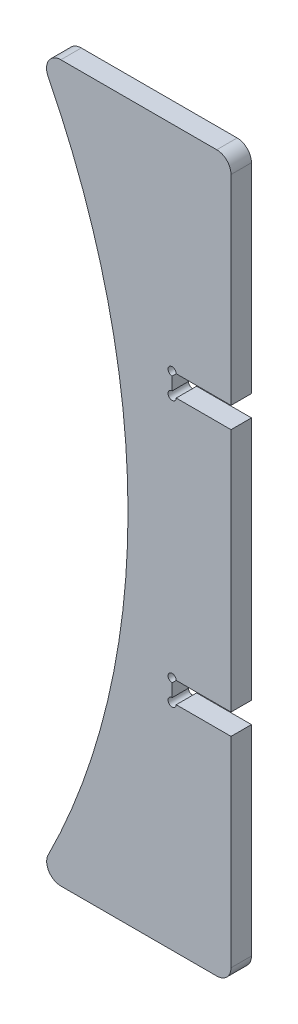
SolidWorks part; units mm, degrees
material "Somente - Acrílico Extrudado"
ref_plane "Front Plane" through (0, 0, 0) normal (0, 0, 1) x (1, 0, 0)
ref_plane "Top Plane" through (0, 0, 0) normal (0, 1, 0) x (1, 0, 0)
ref_plane "Right Plane" through (0, 0, 0) normal (1, 0, 0) x (0, 0, -1)
sketch "Esboço1" plane through (0, 0, 0) normal (0, 0, 1) x (1, 0, 0)
  line L0 (-1.7226, 117.8082) -> (-1.7226, 68.8832)
  line L1 (-1.7226, 68.8832) -> (-16.1382, 68.8832)
  line L2 (-16.1382, 68.8832) -> (-16.1382, 63.7332)
  line L3 (-16.1382, 63.7332) -> (-1.7226, 63.7332)
  line L4 (-1.7226, 63.7332) -> (-1.7226, 3.8832)
  line L5 (-1.7226, 3.8832) -> (-16.1382, 3.8832)
  line L6 (-16.1382, 3.8832) -> (-16.1382, -1.2668)
  line L7 (-16.1382, -1.2668) -> (-1.7226, -1.2668)
  line L8 (-1.7226, -1.2668) -> (-1.7226, -50.3157)
  line L9 (-5.2226, -53.8157) -> (-43.3387, -53.8157)
  line L10 (-43.372, 121.3082) -> (-5.2226, 121.3082)
  arc A0 (-5.2226, -53.8157) -> (-1.7226, -50.3157) centre (-5.2226, -50.3157) ccw
  arc A1 (-46.5872, -49.0131) -> (-43.3387, -53.8157) centre (-43.3387, -50.3157) ccw
  arc A2 (-46.5872, -49.0131) -> (-46.4995, 116.237) centre (-210.7899, 33.6992) ccw
  arc A3 (-43.372, 121.3082) -> (-46.4995, 116.237) centre (-43.372, 117.8082) ccw
  arc A4 (-1.7226, 117.8082) -> (-5.2226, 121.3082) centre (-5.2226, 117.8082) ccw
base flange "Flange-base1" sketch "Esboço1" thickness 5 reverse thickness direction no parameters "D1"=0.1
sketch "Esboço2" plane through (0, 0, 0) normal (0, 0, 1) x (1, 0, 0)
  circle A0 centre (-16.1382, 68.8832) radius 1
  circle A1 centre (-16.1382, 63.7332) radius 1
  circle A2 centre (-16.1382, 3.8832) radius 1
  circle A3 centre (-16.1382, -1.2668) radius 1
  dimension "D1" = 2
extrude "Corte-extrusão1" cut sketch "Esboço2" against normal up to next
sketch "Curva-Linhas1" [suppressed] plane through (0, 0, 0) normal (0, 1, 0) x (1, 0, 0)
sketch "Caixa delimitadora1" [suppressed] plane through (0, 0, 0) normal (0, 1, 0) x (1, 0, 0)
sheet metal parameters "Chapa metálica6" thickness 5 parameters "D1"=0.1
flat pattern "Padrão-Plano6" [suppressed]
sketch "Curva-Linhas2" plane through (0, 0, 0) normal (0, 1, 0) x (1, 0, 0)
sketch3d "Caixa delimitadora2" [suppressed]
  line L0 (3.5, 3.5, 0) -> (3.5, -171.6239, 0) construction
  line L1 (-41.6494, 3.5, 0) -> (-41.6494, -171.6239, 0) construction
  line L2 (3.5, 3.5, 0) -> (-41.6494, 3.5, 0) construction
  line L3 (3.5, -171.6239, 0) -> (-41.6494, -171.6239, 0) construction
sheet metal parameters "Chapa metálica7" thickness 5 parameters "D1"=0.1
flat pattern "Padrão-Plano6"
sketch "Curva-Linhas2" plane through (0, 0, 0) normal (0, 1, 0) x (1, 0, 0)
sketch3d "Caixa delimitadora2" [suppressed]
  line L0 (3.5, 3.5, 0) -> (3.5, -171.6239, 0) construction
  line L1 (-41.6494, 3.5, 0) -> (-41.6494, -171.6239, 0) construction
  line L2 (3.5, 3.5, 0) -> (-41.6494, 3.5, 0) construction
  line L3 (3.5, -171.6239, 0) -> (-41.6494, -171.6239, 0) construction
